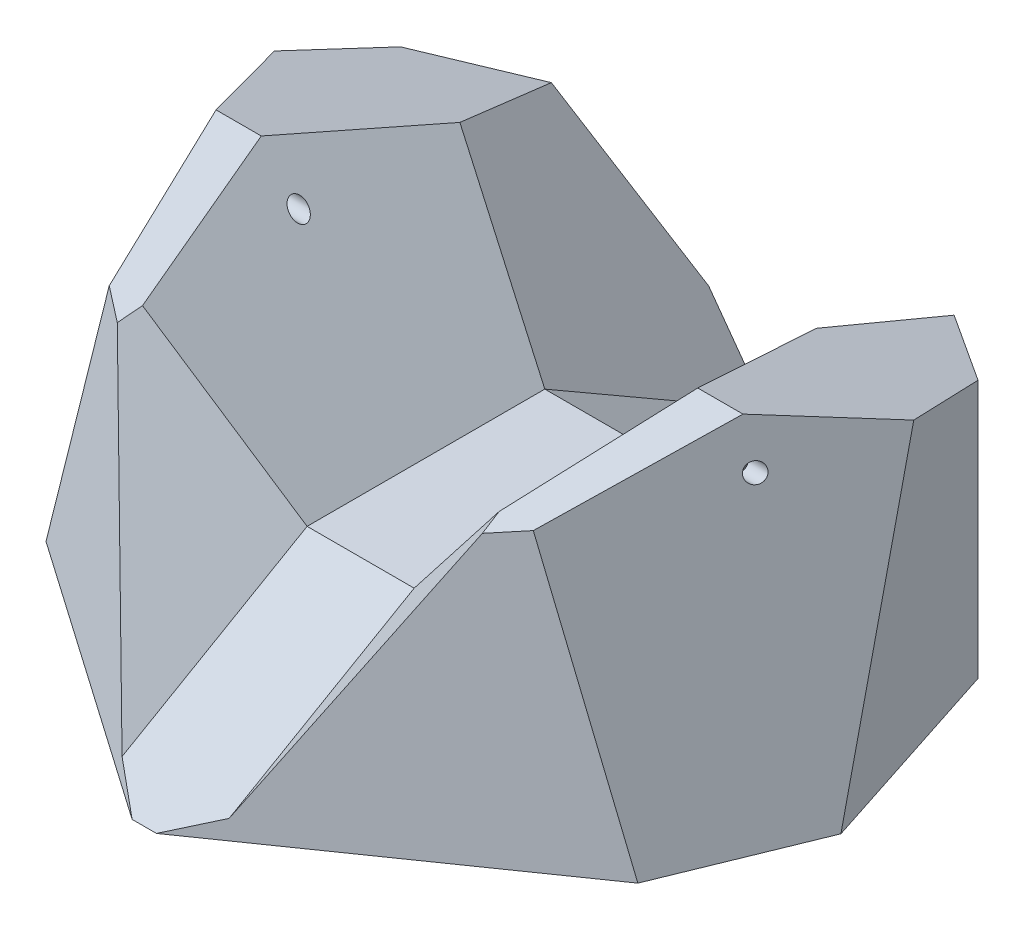
SolidWorks part; units mm, degrees
ref_plane "Plan de face" through (0, 0, 0) normal (0, 0, 1) x (1, 0, 0)
ref_plane "Plan de dessus" through (0, 0, 0) normal (0, 1, 0) x (1, 0, 0)
ref_plane "Plan de droite" through (0, 0, 0) normal (1, 0, 0) x (0, 0, -1)
sketch "Esquisse1" plane through (0, 0, 0) normal (0, 0, 1) x (1, 0, 0)
  line L1 (0, 0) -> (400, 0)
  line L2 (0, 0) -> (0, 120)
  line L3 (0, 120) -> (400, 120)
  line L4 (400, 0) -> (400, 120)
  dimension "D1" = 120
  dimension "D2" = 400
extrude "Boss.-Extru.1" add sketch "Esquisse1" along normal blind 400
sketch "Esquisse7" plane through (0, 0, 0) normal (-1, 0, 0) x (0, 0, 1)
  line L0 (200, 120) -> (200, 180) construction
  line L1 (400, 120) -> (0, 120) construction
  line L2 (200, 180) -> (0, 120)
  line L3 (0, 120) -> (400, 120)
  line L4 (200, 180) -> (400, 120)
  dimension "D1" = 60
extrude "Boss.-Extru.2" add sketch "Esquisse7" against normal up to surface (400 mm away) up to face at (400, 60, 200)
sketch "Esquisse10" plane through (0, 0, 400) normal (0, 0, 1) x (1, 0, 0)
  line L0 (200, 120) -> (200, 180) construction
  line L1 (400, 120) -> (0, 120) construction
  line L2 (400, 180) -> (0, 180) construction
  line L3 (200, 120) -> (200, 70) construction
  line L4 (230, 70) -> (170, 70)
  line L5 (170, 70) -> (77.699, 180)
  line L6 (77.699, 180) -> (0, 180)
  line L7 (0, 180) -> (0, 243.2604)
  line L8 (0, 243.2604) -> (400, 243.2604)
  line L9 (200, 243.2604) -> (200, 180) construction
  line L10 (400, 180) -> (400, 243.2604)
  line L11 (322.301, 180) -> (400, 180)
  line L12 (230, 70) -> (322.301, 180)
  dimension "D1" = 110
  dimension "D2" = 30
  dimension "0" = 50
extrude "Enlèv. mat.-Extru.6" cut sketch "Esquisse10" against normal through all
ref_plane "Plan1" through (0, -143.2051, 248.0385) normal (0, -0.5, 0.866) x (-1, 0, 0)
sketch "Esquisse13" plane through (0, -1068.8973, -286.4102) normal (0, 0.5, -0.866) x (1, 0, 0)
  line L0 (322.301, -1372.8203) -> (200, -1372.8203) construction
  line L1 (200, -1372.8203) -> (77.699, -1372.8203) construction
  line L2 (400, -1372.8203) -> (271.955, -1372.8203) construction
  line L3 (200, -1372.8203) -> (200, -1262.8203) construction
  line L4 (170, -1262.8203) -> (230, -1262.8203)
  line L5 (230, -1262.8203) -> (322.301, -1372.8203)
  line L6 (271.955, -1372.8203) -> (128.045, -1372.8203) construction
  line L7 (0, -1372.8203) -> (0, -1578.1348)
  line L8 (0, -1578.1348) -> (400, -1578.1348)
  line L9 (400, -1372.8203) -> (322.301, -1372.8203)
  line L10 (400, -1372.8203) -> (400, -1578.1348)
  line L11 (0, -1372.8203) -> (77.699, -1372.8203)
  line L12 (170, -1262.8203) -> (77.699, -1372.8203)
  dimension "D1" = 110
  dimension "D2" = 30
  dimension "0" = 50
  dimension "D3" = 50
extrude "Enlèv. mat.-Extru.8" cut sketch "Esquisse13" along normal through all both and the other way through all
ref_plane "Plan2" through (0, 30, 51.9615) normal (0, 0.5, 0.866) x (-1, 0, 0)
sketch "Esquisse15" plane through (0, 941.7691, -474.4486) normal (0, -0.5, -0.866) x (-1, 0, 0)
  line L0 (-322.301, -948.8973) -> (-200, -948.8973) construction
  line L1 (-200, -948.8973) -> (-77.699, -948.8973) construction
  line L3 (-200, -948.8973) -> (-200, -1058.8973) construction
  line L4 (-170, -1058.8973) -> (-230, -1058.8973)
  line L5 (-230, -1058.8973) -> (-322.301, -948.8973)
  line L6 (-322.301, -948.8973) -> (-456.7743, -948.8973)
  line L7 (-456.7743, -948.8973) -> (-456.7743, -558.0308)
  line L8 (-456.7743, -558.0308) -> (83.0423, -558.0308)
  line L9 (-77.699, -948.8973) -> (83.0423, -948.8973)
  line L10 (83.0423, -948.8973) -> (83.0423, -558.0308)
  line L11 (-128.045, -948.8973) -> (-271.955, -948.8973) construction
  line L12 (-170, -1058.8973) -> (-77.699, -948.8973)
  dimension "D1" = 110
  dimension "D2" = 30
  dimension "0" = 50
  dimension "D3" = 50
extrude "Enlèv. mat.-Extru.9" cut sketch "Esquisse15" against normal through all both and the other way through all
sketch "Esquisse5" plane through (0, 0, 0) normal (0, 1, 0) x (1, 0, 0)
  line L0 (0, -200) -> (400, -200) construction
  line L3 (400, -400) -> (400, 0) construction
  line L4 (0, -200) -> (38.1966, -317.5571)
  line L5 (38.1966, -317.5571) -> (138.1966, -390.2113)
  line L6 (138.1966, -390.2113) -> (261.8034, -390.2113)
  line L7 (261.8034, -390.2113) -> (361.8034, -317.5571)
  line L8 (361.8034, -317.5571) -> (400, -200)
  line L9 (400, -200) -> (361.8034, -82.4429)
  line L10 (361.8034, -82.4429) -> (261.8034, -9.7887)
  line L11 (261.8034, -9.7887) -> (138.1966, -9.7887)
  line L12 (138.1966, -9.7887) -> (38.1966, -82.4429)
  line L13 (38.1966, -82.4429) -> (0, -200)
  line L15 (0, -400) -> (0, 0) construction
  circle A0 centre (200, -200) radius 190.2113 construction
  circle A1 centre (183.3597, -200) radius 378.4677
extrude "Enlèv. mat.-Extru.3" cut sketch "Esquisse5" along normal blind 300
chamfer "Chanfrein1" distance 50 angle 70 4 edges at (337.3281, 139.3982, 335.3394) (62.6719, 139.3982, 335.3394) (19.0983, 162.3664, 258.7785) (380.9017, 162.3664, 258.7785) first distance on face at (339.3744, 158.4236, 271.9214) first distance on face at (60.6256, 158.4236, 271.9214)
shell "Coque1" thickness 10
sketch "Esquisse16" plane through (0, 0, 0) normal (1, 0, 0) x (0, 0, -1)
  line L0 (-200, 180) -> (-200, 0) construction
  line L1 (-196.2568, 0) -> (-277.0897, 0) construction
  circle A0 centre (-200, 155) radius 5
  dimension "D1" = 10
  dimension "D2" = 25
extrude "Enlèv. mat.-Extru.10" cut sketch "Esquisse16" along normal through all
